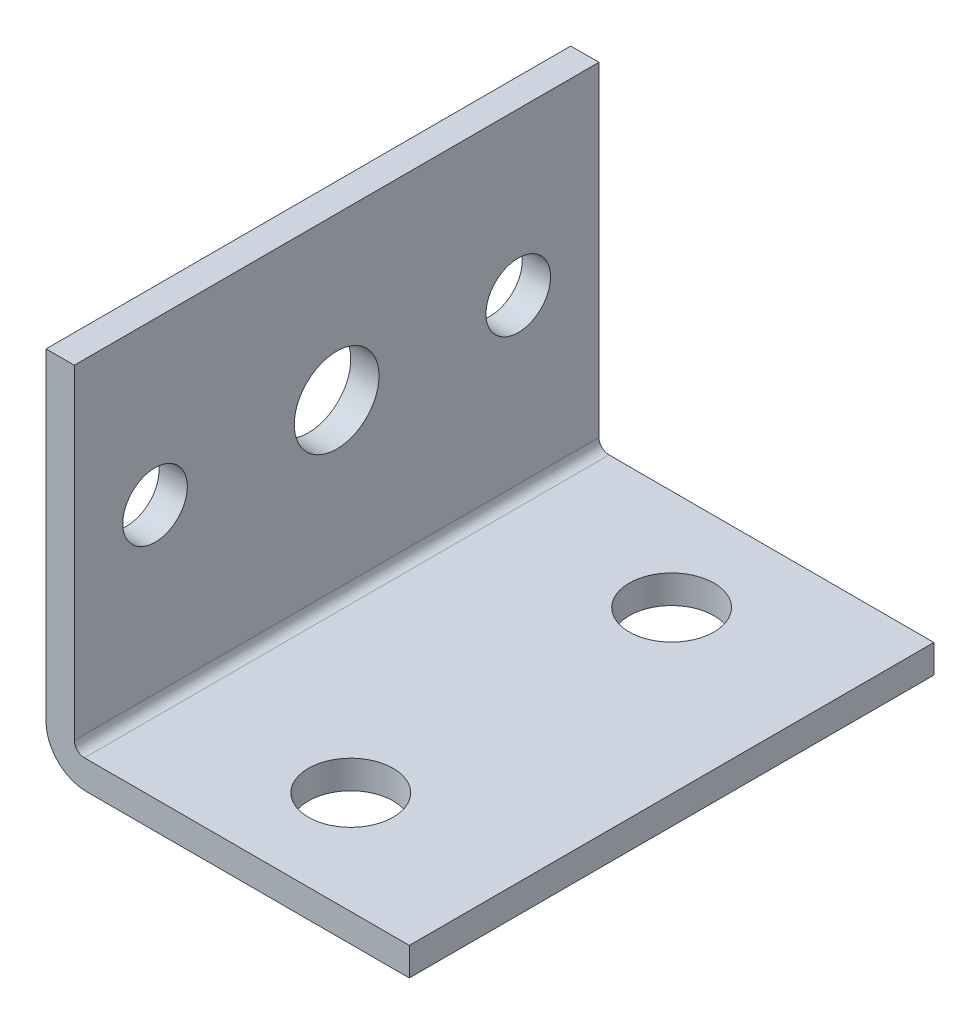
SolidWorks part; units mm, degrees
material "Plain Carbon Steel"
ref_plane "Front Plane" through (0, 0, 0) normal (0, 0, 1) x (1, 0, 0)
ref_plane "Top Plane" through (0, 0, 0) normal (0, 1, 0) x (1, 0, 0)
ref_plane "Right Plane" through (0, 0, 0) normal (1, 0, 0) x (0, 0, -1)
sketch "Sketch1" plane through (0, 0, 0) normal (0, 0, 1) x (1, 0, 0)
  line L0 (-20.6342, 26.4531) -> (-20.6342, -19.2669)
  line L1 (-20.6342, -19.2669) -> (25.0858, -19.2669)
  line L2 (25.0858, -19.2669) -> (25.0858, -15.7109)
  line L3 (-20.6342, 26.4531) -> (-17.0782, 26.4531)
  line L4 (-17.0782, -15.7109) -> (-17.0782, 26.4531)
  line L5 (-17.0782, -15.7109) -> (25.0858, -15.7109)
  line L6 (25.0858, -15.7109) -> (24.797, -15.8594)
extrude "Boss-Extrude1" add sketch "Sketch1" against normal blind 66.04 contours L5 L4 L3 L0 L1 L2 region at (-18.8562, 25.8065, 0)
fillet "Fillet1" radius 1.27 1 edges at (-17.0782, -15.7109, -33.02)
fillet "Fillet3" radius 5.08 1 edges at (-20.6342, -19.2669, -33.02)
sketch "Sketch2" plane through (-20.6342, 0, 0) normal (-1, 0, 0) x (0, 0, 1)
  circle A0 centre (-33.02, 6.1331) radius 5.334
  circle A1 centre (-55.88, 6.1331) radius 4.064
  circle A2 centre (-10.16, 6.1331) radius 4.064
extrude "Cut-Extrude1" cut sketch "Sketch2" against normal blind 66.04
sketch "Sketch3" plane through (0, -19.2669, 0) normal (0, -1, 0) x (-1, 0, 0)
  circle A0 centre (-4.7658, 12.954) radius 5.334
  circle A1 centre (-4.7658, 53.34) radius 5.334
extrude "Cut-Extrude2" cut sketch "Sketch3" against normal blind 66.04
